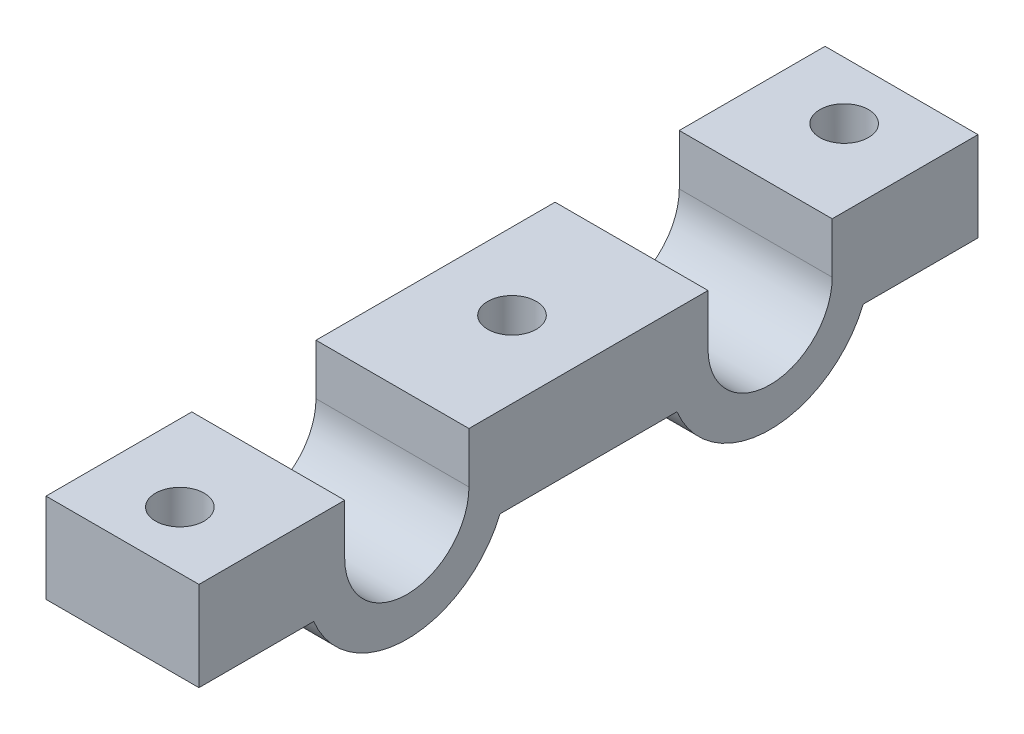
SolidWorks part; units mm, degrees
ref_plane "Front Plane" through (0, 0, 0) normal (0, 0, 1) x (1, 0, 0)
ref_plane "Top Plane" through (0, 0, 0) normal (0, 1, 0) x (1, 0, 0)
ref_plane "Right Plane" through (0, 0, 0) normal (1, 0, 0) x (0, 0, -1)
sketch "Sketch2" plane through (0, 0, 0) normal (1, 0, 0) x (0, 0, -1)
  line L0 (-15.24, 0) -> (15.24, 0) construction
  line L1 (-16.24, 0) -> (-54.3667, 0) construction
  line L2 (16.24, 0) -> (78.76, 0) construction
  line L3 (0, 0) -> (95, 0) construction
  line L4 (111.24, 0) -> (149.3667, 0) construction
  line L5 (-24.3667, -10.16) -> (-54.3667, -10.16)
  line L6 (24.3667, -10.16) -> (70.6333, -10.16)
  line L7 (119.3667, -10.16) -> (149.3667, -10.16)
  line L8 (-54.3667, 0) -> (-54.3667, -10.16)
  line L9 (149.3667, 0) -> (149.3667, -10.16)
  line L10 (-54.3667, 0) -> (-54.3667, 13.24)
  line L11 (-54.3667, 13.24) -> (-16.24, 13.24)
  line L12 (-16.24, 13.24) -> (-16.24, 0)
  line L13 (16.24, 0) -> (16.24, 13.24)
  line L14 (16.24, 13.24) -> (78.76, 13.24)
  line L15 (78.76, 13.24) -> (78.76, 0)
  line L16 (111.24, 0) -> (111.24, 13.24)
  line L17 (111.24, 13.24) -> (149.3667, 13.24)
  line L18 (149.3667, 13.24) -> (149.3667, 0)
  arc A0 (-15.24, 0) -> (15.24, 0) centre (0, 0) ccw construction
  arc A1 (-16.24, 0) -> (16.24, 0) centre (0, 0) ccw
  arc A2 (79.76, 0) -> (110.24, 0) centre (95, 0) ccw construction
  arc A3 (78.76, 0) -> (111.24, 0) centre (95, 0) ccw
  arc A4 (-24.3667, -10.16) -> (24.3667, -10.16) centre (0, 0) ccw
  arc A5 (70.6333, -10.16) -> (119.3667, -10.16) centre (95, 0) ccw
  point P27 (0, 0)
  point P30 (0, 0)
  dimension "D6" = 10.16
  dimension "D1" = 30.48
  dimension "D3" = 95
  dimension "D5" = 30
  dimension "D7" = 10.16
  dimension "D8" = 10.16
  dimension "D9" = 13.24
  dimension "D2" = 1
  dimension "D4" = 1
extrude "Boss-Extrude1" add sketch "Sketch2" along normal blind 40
sketch "Sketch3" plane through (0, 13.24, 0) normal (0, 1, 0) x (1, 0, 0)
  line L0 (0, -54.3667) -> (0, -24.3667) construction
  line L1 (0, -54.3667) -> (0, -24.3667) construction
  line L3 (40, -54.3667) -> (0, -54.3667) construction
  line L5 (40, 78.76) -> (40, 16.24) construction
  line L8 (40, -54.3667) -> (0, -54.3667) construction
  line L9 (40, -16.24) -> (40, -54.3667) construction
  line L10 (0, 78.76) -> (0, 16.24) construction
  line L11 (40, 16.24) -> (0, 16.24) construction
  line L16 (40, 16.24) -> (0, 16.24) construction
  line L18 (40, 78.76) -> (40, 16.24) construction
  line L19 (0, 78.76) -> (0, 16.24) construction
  line L24 (0, 47.5) -> (40, 47.5) construction
  line L25 (40, 78.76) -> (0, 78.76) construction
  circle A0 centre (20, -39.3667) radius 6.35
  circle A1 centre (20, 134.3667) radius 6.35
  circle A2 centre (20, 47.5) radius 6.35
  point P6 (0, -39.3667)
  point P14 (20, -54.3667)
  point P15 (40, 77.4225)
  point P23 (49.7404, -54.3667)
  point P24 (0, 0)
  point P31 (40, 43.9102)
  point P32 (0, 0)
  point P35 (20, 133.0292)
  dimension "D1" = 12.7
extrude "Cut-Extrude1" cut sketch "Sketch3" against normal up to next
